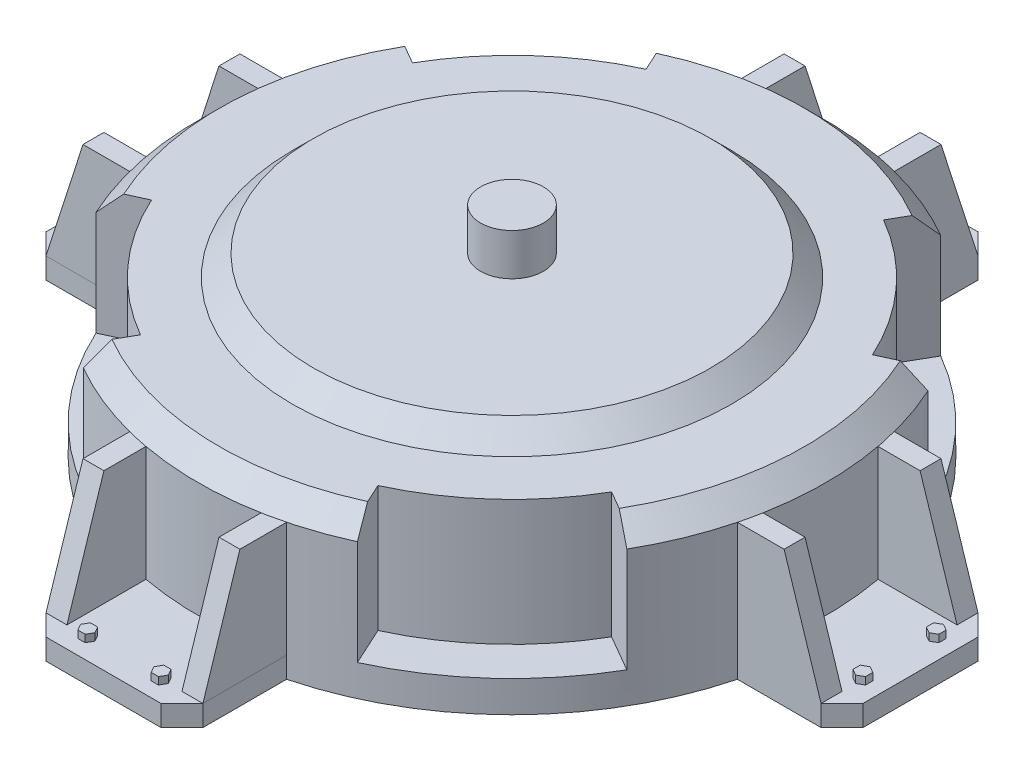
SolidWorks part; units mm, degrees
material "AISI Type 316L stainless steel"
ref_plane "Front Plane" through (0, 0, 0) normal (0, 0, 1) x (1, 0, 0)
ref_plane "Top Plane" through (0, 0, 0) normal (0, 1, 0) x (1, 0, 0)
ref_plane "Right Plane" through (0, 0, 0) normal (1, 0, 0) x (0, 0, -1)
sketch "Sketch1" plane through (0, 0, 0) normal (0, 1, 0) x (1, 0, 0)
  circle A0 centre (0, 0) radius 150
  dimension "D1" = 300
extrude "Boss-Extrude1" add sketch "Sketch1" along normal blind 75
chamfer "Chamfer1" distance 10 angle 45 1 edges at (0, 75, 150)
sketch "Sketch2" plane through (0, 0, 0) normal (0, -1, 0) x (1, 0, 0)
  line L1 (-145.2369, -37.5) -> (-195.2369, -37.5)
  line L3 (-145.2369, 37.5) -> (-195.2369, 37.5)
  line L4 (-195.2369, -37.5) -> (-195.2369, 37.5)
  line L5 (-150, 0) -> (-195.2369, 37.5) construction
  line L6 (-150, 0) -> (-195.2369, -37.5) construction
  circle A0 centre (0, 0) radius 150 construction
  arc A1 (-145.2369, 37.5) -> (-145.2369, -37.5) centre (0, 0) ccw
  point P0 (-150, 0)
  dimension "D1" = 75
  dimension "D2" = 50
extrude "Boss-Extrude2" add sketch "Sketch2" against normal blind 10
chamfer "Chamfer2" distance 10 angle 45 2 edges at (-195.2369, 5, 37.5) (-195.2369, 5, -37.5)
sketch "Sketch3" plane through (0, 0, 37.5) normal (0, 0, 1) x (1, 0, 0)
  line L0 (-185.2369, 10) -> (-145.2369, 10)
  line L1 (-145.2369, 10) -> (-145.2369, 65)
  line L2 (-150, 65) -> (150, 65) construction
  line L3 (-145.2369, 65) -> (-167.5569, 65)
  line L4 (-167.5569, 65) -> (-185.2369, 10)
  dimension "D1" = 17.68
extrude "Boss-Extrude3" add sketch "Sketch3" against normal blind 10 separate body
sketch "Sketch4" plane through (0, 10, 0) normal (0, 1, 0) x (1, 0, 0)
  line L0 (-185.2369, -82.5107) -> (-185.2369, 37.5) construction
  line L2 (-185.2369, -14.0657) -> (-188.2369, -15.7978)
  line L3 (-188.2369, -15.7978) -> (-188.2369, -19.2619)
  line L4 (-188.2369, -19.2619) -> (-185.2369, -20.9939)
  line L5 (-185.2369, -20.9939) -> (-182.2369, -19.2619)
  line L6 (-182.2369, -19.2619) -> (-182.2369, -15.7978)
  line L7 (-182.2369, -15.7978) -> (-185.2369, -14.0657)
  circle A0 centre (-185.2369, -17.5298) radius 3 construction
  point P3 (0, 0)
  point P12 (-185.2369, -23.1189)
  point P13 (-185.2369, -19.5481)
  point P14 (-185.2369, -17.5298)
  dimension "D1" = 6
extrude "Boss-Extrude4" add sketch "Sketch4" along normal blind 3.5
mirror "Mirror1" about plane through (0, 0, 0) normal (0, 0, 1) of "Boss-Extrude3", "Boss-Extrude4"
pattern_circular "CirPattern8" count 4 over 360 about axis through (0, 0, 0) along (0, 1, 0) of bodies 106 105
sketch "Sketch5" plane through (0, 75, 0) normal (0, 1, 0) x (1, 0, 0)
  line L2 (-118.1912, -54.1371) -> (-136.3745, -62.4659)
  line L3 (-65, -112.5833) -> (-75, -129.9038)
  arc A0 (-118.1912, -54.1371) -> (-65, -112.5833) centre (0, 0) ccw
  arc A1 (147.4576, -27.5) -> (145.2369, -37.5) centre (0, 0) ccw construction
  arc A2 (-136.3745, -62.4659) -> (-75, -129.9038) centre (0, 0) ccw
  dimension "D3" = 260
extrude "Cut-Extrude1" cut sketch "Sketch5" against normal blind 60
sketch "Sketch6" plane through (0, 75, 0) normal (0, 1, 0) x (1, 0, 0)
  circle A0 centre (0, 0) radius 110
  dimension "D1" = 220
extrude "Boss-Extrude5" add sketch "Sketch6" along normal blind 10
chamfer "Chamfer3" distance 15 angle 45 1 edges at (0, 85, 110)
sketch "Sketch7" plane through (0, 85, 0) normal (0, 1, 0) x (1, 0, 0)
  circle A0 centre (0, 0) radius 15
  dimension "D1" = 30
extrude "Boss-Extrude6" add sketch "Sketch7" along normal blind 20
pattern_circular "CirPattern9" count 4 over 360 about axis through (0, 0, 0) along (0, 1, 0) of "Cut-Extrude1"
